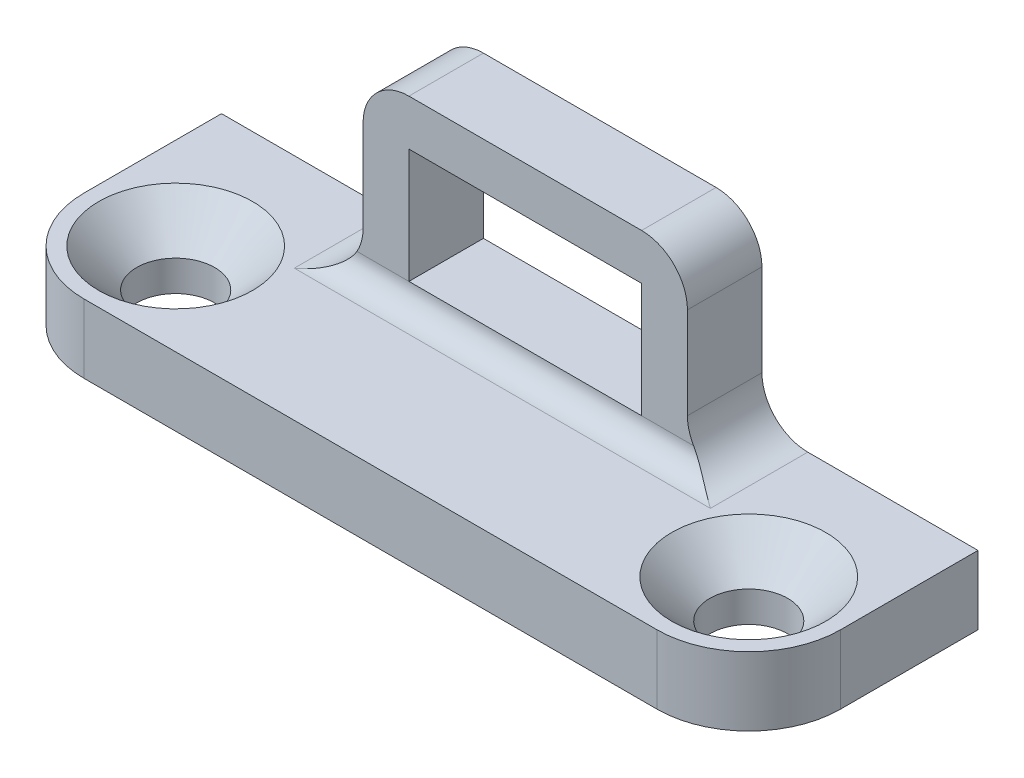
SolidWorks part; units mm, degrees
ref_plane "Front" through (0, 0, 0) normal (0, 0, 1) x (1, 0, 0)
ref_plane "Top" through (0, 0, 0) normal (0, 1, 0) x (1, 0, 0)
ref_plane "Right" through (0, 0, 0) normal (1, 0, 0) x (0, 0, -1)
sketch "Sketch1" plane through (0, 0, 0) normal (0, 1, 0) x (1, 0, 0)
  line L1 (-16.5, 0) -> (16.5, 0)
  line L2 (-16.5, 0) -> (-16.5, -10)
  line L3 (-16.5, -10) -> (16.5, -10)
  line L4 (16.5, 0) -> (16.5, -10)
  dimension "D2" = 33
  dimension "D3" = 10
extrude "Boss-Extrude1" add sketch "Sketch1" along normal blind 3 contours L4 L1 L2 L3 | L1 | L1 region at (0, 0, 5)
sketch "Sketch2" plane through (0, 0, 0) normal (0, 1, 0) x (1, 0, 0)
  line L0 (12.5, -6) -> (-12.5, -6) construction
  line L1 (0, 0) -> (0, -6) construction
  line L3 (-16.5, -10) -> (16.5, -10) construction
  dimension "D1" = 25
  dimension "D2" = 4
hole_wizard "CSK for M3 SFHCS1" positions "Sketch3" profile "Sketch4" countersink size "M3" standard "ANSI Metric"
sketch "Sketch3" plane through (0, 3, 0) normal (0, 1, 0) x (1, 0, 0)
  point P0 (-12.5, -6)
  point P3 (12.5, -6)
sketch "Sketch4" plane through (-12.5, 3, 6) normal (1, 0, 0) x (0, 0, 1)
  line L0 (0, 0) -> (0, 11.0215)
  line L1 (0, 11.0215) -> (1.7, 10)
  line L2 (1.7, 10) -> (1.7, 1.66)
  line L3 (1.7, 1.66) -> (3.36, 0)
  line L5 (3.36, 0) -> (0, 0)
  line L6 (-1.7, 1.66) -> (-3.36, 0) construction
  line L10 (0, 11.0215) -> (-1.7, 10) construction
  line L11 (0, -6.35) -> (0, 107.95) construction
  dimension "Hole Dia." = 3.4
  dimension "Hole Depth" = 10
  dimension "Near C'Sink Dia." = 6.72
  dimension "Near C'Sink Angle" = 90
  dimension "Drill Angle" = 118
fillet "Fillet1" radius 4 2 edges at (-16.5, 1.5, 10) (16.5, 1.5, 10)
sketch "Sketch5" plane through (0, 0, 0) normal (0, 0, -1) x (-1, 0, 0)
  line L0 (0, 0) -> (0, 6.5) construction
  line L2 (-7.075, 3) -> (-7.075, 11)
  line L3 (-7.075, 11) -> (7.075, 11)
  line L4 (7.075, 3) -> (7.075, 11)
  line L5 (16.5, 3) -> (-16.5, 3) construction
  line L6 (-5.075, 9) -> (5.075, 9) construction
  line L7 (-5.075, 9) -> (-5.075, 4) construction
  line L8 (-5.075, 4) -> (5.075, 4) construction
  line L9 (5.075, 9) -> (5.075, 4) construction
  line L10 (-5.075, 9) -> (5.075, 4) construction
  line L19 (-7.075, 3) -> (7.075, 3)
  point P0 (0, 0)
  point P14 (0, 4)
  dimension "D1" = 6.5
  dimension "D2" = 5
  dimension "D4" = 10.15
  dimension "D5" = 2
  dimension "D6" = 2
  dimension "D7" = 2
extrude "Boss-Extrude2" add sketch "Sketch5" against normal blind 3.25
sketch "Sketch6" plane through (0, 0, 3.25) normal (0, 0, 1) x (1, 0, 0)
  line L0 (5.075, 9) -> (-5.075, 9) construction
  line L1 (5.075, 9) -> (5.075, 4) construction
  line L2 (5.075, 4) -> (-5.075, 4) construction
  line L3 (-5.075, 9) -> (-5.075, 4) construction
  line L4 (5.075, 9) -> (-5.075, 9)
  line L5 (5.075, 9) -> (5.075, 4)
  line L6 (5.075, 4) -> (-5.075, 4)
  line L7 (-5.075, 9) -> (-5.075, 4)
extrude "Cut-Extrude1" cut sketch "Sketch6" against normal through all
fillet "Fillet2" radius 2 4 edges at (-7.075, 3, 1.625) (7.075, 3, 1.625) (-7.075, 11, 1.625) (7.075, 11, 1.625)
fillet "Fillet3" radius 1 1 edges at (0, 3, 3.25)
